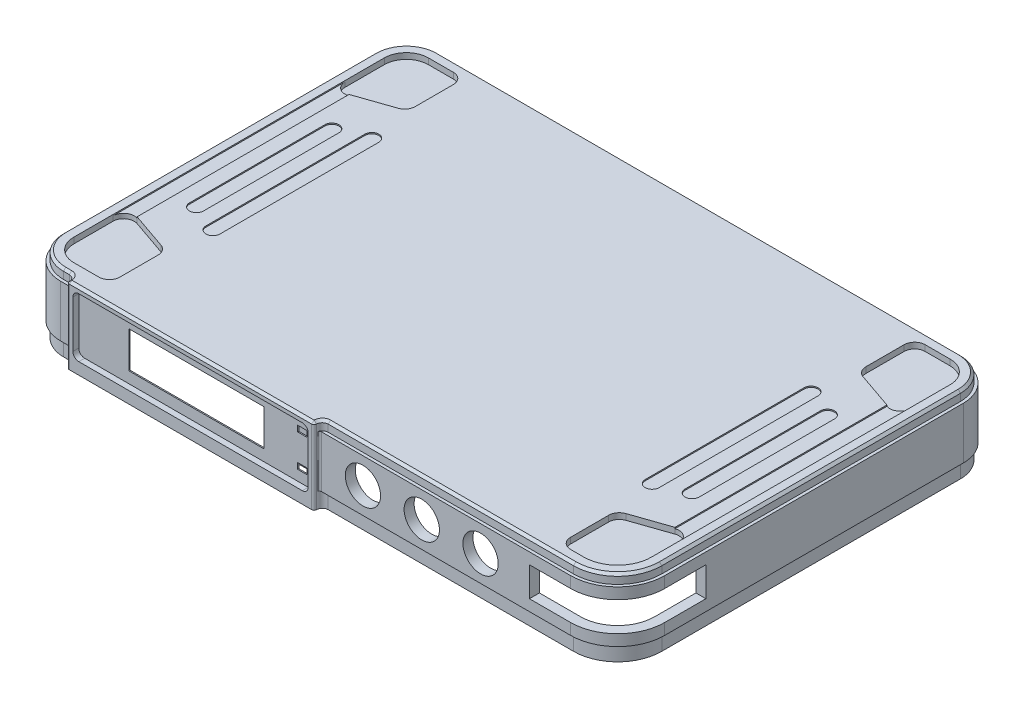
SolidWorks part; units mm, degrees
ref_plane "Front Plane" through (0, 0, 0) normal (0, 0, 1) x (1, 0, 0)
ref_plane "Top Plane" through (0, 0, 0) normal (0, 1, 0) x (1, 0, 0)
ref_plane "Right Plane" through (0, 0, 0) normal (1, 0, 0) x (0, 0, -1)
sketch "Sketch1" plane through (0, 0, 0) normal (0, 1, 0) x (1, 0, 0)
  line L0 (-50.35, 0) -> (50.35, 0) construction
  line L1 (0, 32.39) -> (0, -32.39) construction
  line L8 (44.35, 32.39) -> (-44.35, 32.39)
  line L9 (-50.35, 26.39) -> (-50.35, -26.39)
  line L10 (-44.35, -32.39) -> (42.35, -32.39)
  line L11 (50.35, -24.39) -> (50.35, 26.39)
  arc A2 (42.35, -32.39) -> (50.35, -24.39) centre (42.35, -24.39) ccw
  arc A8 (50.35, 26.39) -> (44.35, 32.39) centre (44.35, 26.39) ccw
  arc A9 (-44.35, 32.39) -> (-50.35, 26.39) centre (-44.35, 26.39) ccw
  arc A10 (-50.35, -26.39) -> (-44.35, -32.39) centre (-44.35, -26.39) ccw
  dimension "D2" = 64.78
  dimension "D3" = 6
  dimension "D1" = 100.7
  dimension "D4" = 0
  dimension "D5" = 8
extrude "Boss-Extrude1" add sketch "Sketch1" along normal blind 13
sketch "Sketch3" plane through (0, 13, 0) normal (0, 1, 0) x (1, 0, 0)
  line L0 (-50.35, 0) -> (50.35, 0) construction
  line L1 (-50.35, 26.39) -> (-50.35, -26.39) construction
  line L2 (42.35, -30.1389) -> (40.0989, -30.1389)
  line L3 (0, -32.39) -> (0, 32.39) construction
  line L4 (-44.35, -32.39) -> (42.35, -32.39) construction
  line L5 (50.35, -24.39) -> (50.35, 26.39) construction
  line L6 (-45.9859, -18.557) -> (-39.9859, -20.6263) construction
  line L8 (-48.0989, -19.7157) -> (-48.0989, -26.39)
  line L9 (-39.5121, -20.1524) -> (-45.7121, -18.014)
  line L10 (-38.2989, -28.3389) -> (-38.2989, -21.854)
  line L11 (-44.35, -30.1389) -> (-40.0989, -30.1389)
  line L13 (44.35, 32.39) -> (-44.35, 32.39) construction
  line L14 (-44.35, 30.1389) -> (-40.0989, 30.1389)
  line L15 (-38.2989, 28.3389) -> (-38.2989, 21.854)
  line L16 (-39.5121, 20.1524) -> (-45.7121, 18.014)
  line L17 (-48.0989, 19.7157) -> (-48.0989, 26.39)
  line L18 (48.0989, 19.7157) -> (48.0989, 26.39)
  line L19 (39.5121, 20.1524) -> (45.7121, 18.014)
  line L20 (38.2989, 28.3389) -> (38.2989, 21.854)
  line L21 (44.35, 30.1389) -> (40.0989, 30.1389)
  line L23 (38.2989, -28.3389) -> (38.2989, -21.854)
  line L24 (39.5121, -20.1524) -> (45.7121, -18.014)
  line L25 (48.0989, -19.7157) -> (48.0989, -24.39)
  arc A0 (-40.0989, 30.1389) -> (-38.2989, 28.3389) centre (-40.0989, 28.3389) cw
  arc A1 (-38.2989, 21.854) -> (-39.5121, 20.1524) centre (-40.0989, 21.854) cw
  arc A2 (-45.7121, 18.014) -> (-48.0989, 19.7157) centre (-46.2989, 19.7157) cw
  arc A3 (-48.0989, 26.39) -> (-44.35, 30.1389) centre (-44.35, 26.39) cw
  arc A4 (-50.35, -26.39) -> (-44.35, -32.39) centre (-44.35, -26.39) ccw construction
  arc A5 (42.35, -32.39) -> (50.35, -24.39) centre (42.35, -24.39) ccw construction
  arc A6 (38.2989, -28.3389) -> (40.0989, -30.1389) centre (40.0989, -28.3389) ccw
  arc A8 (-48.0989, -26.39) -> (-44.35, -30.1389) centre (-44.35, -26.39) ccw
  arc A9 (-45.7121, -18.014) -> (-48.0989, -19.7157) centre (-46.2989, -19.7157) ccw
  arc A10 (-38.2989, -21.854) -> (-39.5121, -20.1524) centre (-40.0989, -21.854) ccw
  arc A11 (-40.0989, -30.1389) -> (-38.2989, -28.3389) centre (-40.0989, -28.3389) ccw
  arc A13 (38.2989, -21.854) -> (39.5121, -20.1524) centre (40.0989, -21.854) cw
  arc A14 (45.7121, -18.014) -> (48.0989, -19.7157) centre (46.2989, -19.7157) cw
  arc A15 (48.0989, -24.39) -> (42.35, -30.1389) centre (42.35, -24.39) cw
  arc A16 (48.0989, 26.39) -> (44.35, 30.1389) centre (44.35, 26.39) ccw
  arc A17 (45.7121, 18.014) -> (48.0989, 19.7157) centre (46.2989, 19.7157) ccw
  arc A18 (38.2989, 21.854) -> (39.5121, 20.1524) centre (40.0989, 21.854) ccw
  arc A19 (40.0989, 30.1389) -> (38.2989, 28.3389) centre (40.0989, 28.3389) ccw
  point P64 (-38.8262, -29.6117)
  point P65 (-47.3438, -18.25)
  point P66 (-38.6333, -20.8091)
  point P67 (-47.0009, -29.0409)
  point P68 (-38.6333, 20.8091)
  point P75 (-47.3438, 18.25)
  dimension "D3" = 36.5
  dimension "D1" = 1.8
  dimension "D6" = 0
  dimension "D7" = 0
  dimension "D2" = 9.8
  dimension "D5" = 14.2
  dimension "D9" = 4.2511
extrude "Cut-Extrude1" cut sketch "Sketch3" against normal blind 1 contours L11 A11 L10 A10 L9 A9 L8 A8 | A15 L25 A14 L24 A13 L23 A6 L2 | L21 A19 L20 A18 L19 A17 L18 A16 | A3 L17 A2 L16 A1 L15 A0 L14 region at (43.195, 13, 24.2277) region at (-43.3228, 13, 24.3948) region at (-43.3228, 13, -24.3948) region at (43.3228, 13, -24.3948)
sketch "Sketch4" plane through (0, 13, 0) normal (0, 1, 0) x (1, 0, 0)
  line L0 (-48.0989, 19.7157) -> (-48.0989, -19.7157)
  line L1 (-45.7121, 0) -> (-48.0989, 0) construction
  line L2 (-40.9252, 0) -> (-43.3121, 0) construction
  line L3 (-42.1186, 11.5066) -> (-42.1186, -11.5066) construction
  line L4 (-40.9252, 11.5066) -> (-40.9252, -11.5066)
  line L5 (-45.7121, 18.014) -> (-45.7121, -18.014)
  line L6 (-43.3121, 11.5066) -> (-43.3121, -11.5066)
  line L7 (-37.3317, 13.5066) -> (-37.3317, -13.5066) construction
  line L8 (-36.1383, 13.5066) -> (-36.1383, -13.5066)
  line L9 (-38.5252, 13.5066) -> (-38.5252, -13.5066)
  line L10 (-36.1383, 0) -> (-38.5252, 0) construction
  line L11 (-45.7121, 0) -> (-43.3121, 0) construction
  line L12 (-40.9252, 0) -> (-38.5252, 0) construction
  line L13 (0, 32.39) -> (0, -32.39) construction
  line L14 (44.35, 32.39) -> (-44.35, 32.39) construction
  line L16 (42.1186, 11.5066) -> (42.1186, -11.5066) construction
  line L17 (40.9252, 11.5066) -> (40.9252, -11.5066)
  line L18 (43.3121, 11.5066) -> (43.3121, -11.5066)
  line L19 (37.3317, 13.5066) -> (37.3317, -13.5066) construction
  line L20 (36.1383, 13.5066) -> (36.1383, -13.5066)
  line L21 (38.5252, 13.5066) -> (38.5252, -13.5066)
  line L22 (40.9252, 0) -> (38.5252, 0) construction
  line L23 (45.7121, 0) -> (43.3121, 0) construction
  line L24 (36.1383, 0) -> (38.5252, 0) construction
  line L25 (40.9252, 0) -> (43.3121, 0) construction
  line L26 (45.7121, 0) -> (48.0989, 0) construction
  line L27 (45.7121, 18.014) -> (45.7121, -18.014)
  line L28 (48.0989, 19.7157) -> (48.0989, -19.7157)
  arc A0 (-48.0989, 19.7157) -> (-45.7121, 18.014) centre (-46.2989, 19.7157) ccw construction
  arc A1 (-45.7121, -18.014) -> (-48.0989, -19.7157) centre (-46.2989, -19.7157) ccw construction
  arc A2 (-48.0989, 19.7157) -> (-45.7121, 18.014) centre (-46.2989, 19.7157) ccw
  arc A3 (-45.7121, -18.014) -> (-48.0989, -19.7157) centre (-46.2989, -19.7157) ccw
  arc A4 (-40.9252, 11.5066) -> (-43.3121, 11.5066) centre (-42.1186, 11.5066) ccw
  arc A5 (-43.3121, -11.5066) -> (-40.9252, -11.5066) centre (-42.1186, -11.5066) ccw
  arc A6 (-36.1383, 13.5066) -> (-38.5252, 13.5066) centre (-37.3317, 13.5066) ccw
  arc A7 (-38.5252, -13.5066) -> (-36.1383, -13.5066) centre (-37.3317, -13.5066) ccw
  arc A8 (40.9252, 11.5066) -> (43.3121, 11.5066) centre (42.1186, 11.5066) cw
  arc A9 (43.3121, -11.5066) -> (40.9252, -11.5066) centre (42.1186, -11.5066) cw
  arc A10 (36.1383, 13.5066) -> (38.5252, 13.5066) centre (37.3317, 13.5066) cw
  arc A11 (38.5252, -13.5066) -> (36.1383, -13.5066) centre (37.3317, -13.5066) cw
  arc A12 (45.7121, -18.014) -> (48.0989, -19.7157) centre (46.2989, -19.7157) cw
  arc A13 (48.0989, 19.7157) -> (45.7121, 18.014) centre (46.2989, 19.7157) cw
  point P4 (-42.1186, 0)
  point P10 (-42.1186, 12.7)
  point P11 (-42.1186, -12.7)
  point P17 (-37.3317, 0)
  point P28 (-37.3317, -14.7)
  point P29 (-37.3317, 14.7)
  point P38 (42.1186, 0)
  point P45 (37.3317, 0)
  point P62 (37.3317, 14.7)
  point P63 (37.3317, -14.7)
  point P64 (42.1186, -12.7)
  point P65 (42.1186, 12.7)
  dimension "D1" = 8.0188
  dimension "D2" = 2.4
  dimension "D3" = 25.4
  dimension "D4" = 29.4
extrude "Cut-Extrude2" cut sketch "Sketch4" against normal blind 0.2
sketch "Sketch5" plane through (0, 13, 0) normal (0, 1, 0) x (1, 0, 0)
  line L0 (44.35, 31.89) -> (-44.35, 31.89)
  line L1 (-49.85, 26.39) -> (-49.85, -26.39)
  line L2 (-44.35, -31.89) -> (42.35, -31.89)
  line L3 (49.85, -24.39) -> (49.85, 26.39)
  line L4 (44.35, 32.39) -> (-44.35, 32.39)
  line L5 (-50.35, 26.39) -> (-50.35, -26.39)
  line L6 (-44.35, -32.39) -> (42.35, -32.39)
  line L7 (50.35, -24.39) -> (50.35, 26.39)
  line L8 (44.35, 32.39) -> (-44.35, 32.39)
  line L9 (-50.35, 26.39) -> (-50.35, -26.39)
  line L10 (-44.35, -32.39) -> (42.35, -32.39)
  line L11 (50.35, -24.39) -> (50.35, 26.39)
  arc A0 (-44.35, 31.89) -> (-49.85, 26.39) centre (-44.35, 26.39) ccw
  arc A1 (-49.85, -26.39) -> (-44.35, -31.89) centre (-44.35, -26.39) ccw
  arc A2 (42.35, -31.89) -> (49.85, -24.39) centre (42.35, -24.39) ccw
  arc A3 (49.85, 26.39) -> (44.35, 31.89) centre (44.35, 26.39) ccw
  arc A4 (50.35, 26.39) -> (44.35, 32.39) centre (44.35, 26.39) ccw
  arc A5 (-44.35, 32.39) -> (-50.35, 26.39) centre (-44.35, 26.39) ccw
  arc A6 (-50.35, -26.39) -> (-44.35, -32.39) centre (-44.35, -26.39) ccw
  arc A7 (42.35, -32.39) -> (50.35, -24.39) centre (42.35, -24.39) ccw
  arc A8 (50.35, 26.39) -> (44.35, 32.39) centre (44.35, 26.39) ccw
  arc A9 (-44.35, 32.39) -> (-50.35, 26.39) centre (-44.35, 26.39) ccw
  arc A10 (-50.35, -26.39) -> (-44.35, -32.39) centre (-44.35, -26.39) ccw
  arc A11 (42.35, -32.39) -> (50.35, -24.39) centre (42.35, -24.39) ccw
  dimension "D2" = 0.5
  dimension "D1" = 0
extrude "Cut-Extrude3" cut sketch "Sketch5" against normal blind 1.6
sketch "Sketch6" plane through (0, 0, 0) normal (0, -1, 0) x (1, 0, 0)
  line L4 (-44.35, -32.39) -> (44.35, -32.39)
  line L5 (-50.35, 26.39) -> (-50.35, -26.39)
  line L6 (42.35, 32.39) -> (-44.35, 32.39)
  line L7 (50.35, -26.39) -> (50.35, 24.39)
  line L8 (-44.35, -32.39) -> (44.35, -32.39)
  line L9 (-50.35, 26.39) -> (-50.35, -26.39)
  line L10 (42.35, 32.39) -> (-44.35, 32.39)
  line L11 (50.35, -26.39) -> (50.35, 24.39)
  line L12 (49.85, -26.39) -> (49.85, 24.39)
  line L13 (-44.35, -31.89) -> (44.35, -31.89)
  line L14 (-49.85, 26.39) -> (-49.85, -26.39)
  line L15 (42.35, 31.89) -> (-44.35, 31.89)
  line L16 (49.85, -26.39) -> (49.85, 24.39)
  line L17 (-44.35, -31.89) -> (44.35, -31.89)
  line L18 (-49.85, 26.39) -> (-49.85, -26.39)
  line L19 (42.35, 31.89) -> (-44.35, 31.89)
  arc A4 (44.35, -32.39) -> (50.35, -26.39) centre (44.35, -26.39) ccw
  arc A5 (-50.35, -26.39) -> (-44.35, -32.39) centre (-44.35, -26.39) ccw
  arc A6 (-44.35, 32.39) -> (-50.35, 26.39) centre (-44.35, 26.39) ccw
  arc A7 (50.35, 24.39) -> (42.35, 32.39) centre (42.35, 24.39) ccw
  arc A8 (44.35, -32.39) -> (50.35, -26.39) centre (44.35, -26.39) ccw
  arc A9 (-50.35, -26.39) -> (-44.35, -32.39) centre (-44.35, -26.39) ccw
  arc A10 (-44.35, 32.39) -> (-50.35, 26.39) centre (-44.35, 26.39) ccw
  arc A11 (50.35, 24.39) -> (42.35, 32.39) centre (42.35, 24.39) ccw
  arc A12 (44.35, -31.89) -> (49.85, -26.39) centre (44.35, -26.39) ccw
  arc A13 (-49.85, -26.39) -> (-44.35, -31.89) centre (-44.35, -26.39) ccw
  arc A14 (-44.35, 31.89) -> (-49.85, 26.39) centre (-44.35, 26.39) ccw
  arc A15 (49.85, 24.39) -> (42.35, 31.89) centre (42.35, 24.39) ccw
  arc A16 (44.35, -31.89) -> (49.85, -26.39) centre (44.35, -26.39) ccw
  arc A17 (-49.85, -26.39) -> (-44.35, -31.89) centre (-44.35, -26.39) ccw
  arc A18 (-44.35, 31.89) -> (-49.85, 26.39) centre (-44.35, 26.39) ccw
  arc A19 (49.85, 24.39) -> (42.35, 31.89) centre (42.35, 24.39) ccw
  dimension "D1" = 0
  dimension "D2" = 0
extrude "Cut-Extrude4" cut sketch "Sketch6" against normal blind 2.6
sketch "Sketch7" plane through (0, 0, 31.89) normal (0, 0, 1) x (1, 0, 0)
  line L0 (-44.35, 13) -> (42.35, 13) construction
  line L1 (-42.35, 13) -> (-0.35, 13)
  line L2 (-42.35, 13) -> (-42.35, 0)
  line L3 (-42.35, 0) -> (-0.35, 0)
  line L4 (-0.35, 13) -> (-0.35, 0)
  line L5 (-42.35, 13) -> (-0.35, 0) construction
  line L6 (-42.35, 0) -> (-0.35, 13) construction
  line L7 (42.35, 0) -> (-44.35, 0) construction
  line L8 (-50.35, 11.4) -> (-50.35, 2.6) construction
  point P0 (-21.35, 6.5)
  dimension "D1" = 42
  dimension "D2" = 8
extrude "Boss-Extrude2" add sketch "Sketch7" along normal blind 1.4
sketch "Sketch8" plane through (-49.85, 0, 0) normal (-1, 0, 0) x (0, 0, 1)
  line L0 (0, 0) -> (0, 13) construction
  line L1 (26.39, 0) -> (-26.39, 0) construction
  line L2 (-26.39, 13) -> (26.39, 13) construction
  line L4 (-18, 11.4) -> (-18, 2.6) construction
  line L5 (-26.39, 11.4) -> (26.39, 11.4) construction
  line L6 (26.39, 2.6) -> (-26.39, 2.6) construction
  circle A0 centre (-18, 7) radius 6
  circle A1 centre (18, 7) radius 6
  circle A2 centre (0, 7) radius 6
  point P8 (-24, 7)
  point P13 (-7.39, 6.5)
  point P16 (7.39, 6.5)
  point P17 (24, 7)
  line M5 (-26.39, 11.4) -> (26.39, 11.4)
  dimension "D1" = 12
  dimension "D2" = 18
extrude "Cut-Extrude6" cut sketch "Sketch8" along normal up to surface (0.5 mm away) contours A0 M5 | A1 M5 | A2 M5 region at (-49.85, 6.5654, -18) region at (-49.85, 6.5654, 18) region at (-49.85, 6.5654, 0) up to face at (-50.35, 7, 0)
sketch "Sketch9" plane through (0, 0, 33.29) normal (0, 0, 1) x (1, 0, 0)
  line L0 (-42.35, 0) -> (-0.35, 0) construction
  line L1 (-40.35, 12) -> (-2.35, 12)
  line L2 (-41.35, 11) -> (-41.35, 3)
  line L3 (-40.35, 2) -> (-2.35, 2)
  line L4 (-1.35, 11) -> (-1.35, 3)
  line L5 (-41.35, 12) -> (-1.35, 2) construction
  line L6 (-41.35, 2) -> (-1.35, 12) construction
  line L7 (-42.35, 7) -> (-0.35, 7) construction
  line L8 (-42.35, 11.4) -> (-42.35, 2.6) construction
  line L9 (-0.35, 2.6) -> (-0.35, 11.4) construction
  line L10 (-21.35, 13) -> (-21.35, 0) construction
  line L11 (-0.35, 13) -> (-42.35, 13) construction
  arc A0 (-40.35, 12) -> (-41.35, 11) centre (-40.35, 11) ccw
  arc A1 (-41.35, 3) -> (-40.35, 2) centre (-40.35, 3) ccw
  arc A2 (-1.35, 3) -> (-2.35, 2) centre (-2.35, 3) cw
  arc A3 (-2.35, 12) -> (-1.35, 11) centre (-2.35, 11) cw
  point P0 (-21.35, 7)
  dimension "D4" = 1
  dimension "D1" = 2
  dimension "D2" = 10
  dimension "D3" = 40
extrude "Cut-Extrude7" cut sketch "Sketch9" against normal blind 1
sketch "Sketch10" plane through (0, 0, -31.89) normal (0, 0, -1) x (-1, 0, 0)
  line L0 (-23.85, 6.5) -> (-34.85, 6.5) construction
  line L1 (-23.85, 0) -> (-34.85, 0)
  line L2 (-23.85, 13) -> (-34.85, 13)
  line L3 (-29.35, 11.4) -> (-29.35, 2.6) construction
  line L4 (-44.35, 11.4) -> (44.35, 11.4) construction
  line L5 (-50.35, 11.4) -> (-50.35, 2.6) construction
  line L6 (44.35, 2.6) -> (-44.35, 2.6) construction
  line L7 (44.35, 0) -> (-44.35, 0) construction
  line L9 (50.35, 11.4) -> (50.35, 2.6) construction
  line L10 (-44.35, 13) -> (44.35, 13) construction
  arc A0 (-23.85, 0) -> (-23.85, 13) centre (-23.85, 6.5) ccw
  arc A1 (-34.85, 13) -> (-34.85, 0) centre (-34.85, 6.5) ccw
  circle A2 centre (33.85, 6.5) radius 6.5
  circle A3 centre (-34.85, 6.5) radius 5 construction
  point P2 (-29.35, 6.5)
  point P7 (-17.35, 6.5)
  point P14 (-41.35, 6.5)
  point P23 (-34.85, 11.5)
  point P24 (40.35, 6.5)
  dimension "D2" = 24
  dimension "D3" = 11
  dimension "D5" = 1.5
  dimension "D6" = 10
  dimension "D1" = 9
  dimension "D4" = 10
extrude "Cut-Extrude8" cut sketch "Sketch10" along normal up to surface (0.5 mm away) up to face at (0, 7, -32.39)
fillet "Fillet1" radius 0.4 4 edges at (-42.35, 7, 32.39) (-42.35, 6.5, 33.29) (-0.35, 7, 32.39) (-0.35, 6.5, 33.29)
fillet "Fillet2" radius 1 2 edges at (-0.35, 12.2, 31.89) (-42.35, 12.2, 31.89)
chamfer "Chamfer1" distance 0.4 angle 45 14 edges at (0, 13, -31.89) (48.2391, 13, -30.2791) (-48.2391, 13, -30.2791) (49.85, 13, -1) (-49.85, 13, 0) (47.6533, 13, 29.6933) (-48.2391, 13, 30.2791) (21.5, 13, 31.89) (-43.85, 13, 31.89) (-0.0571, 13, 32.1829) (-42.6429, 13, 32.1829) (-0.4672, 13, 33.1728) (-42.2328, 13, 33.1728) (-21.35, 13, 33.29)
sketch "Sketch11" plane through (0, 0, 0) normal (0, -1, 0) x (1, 0, 0)
  line L6 (-0.75, 33.29) -> (-41.95, 33.29)
  line L7 (-0.75, 33.29) -> (-41.95, 33.29)
  line L8 (-43.35, 31.89) -> (-44.35, 31.89)
  line L9 (-43.35, 31.89) -> (-44.35, 31.89)
  line L10 (-49.85, 26.39) -> (-49.85, -26.39)
  line L11 (-49.85, 26.39) -> (-49.85, -26.39)
  line L18 (-1.3994, 32.09) -> (-41.3006, 32.09)
  line L19 (-43.35, 30.69) -> (-44.35, 30.69)
  line L20 (-48.65, 26.39) -> (-48.65, -26.39)
  line L21 (-44.35, -30.69) -> (44.35, -30.69)
  line L22 (48.65, -26.39) -> (48.65, 24.39)
  line L23 (42.35, 30.69) -> (0.65, 30.69)
  line L24 (-44.35, -31.89) -> (44.35, -31.89)
  line L25 (-44.35, -31.89) -> (44.35, -31.89)
  line L26 (49.85, -26.39) -> (49.85, 24.39)
  line L27 (49.85, -26.39) -> (49.85, 24.39)
  line L28 (42.35, 31.89) -> (0.65, 31.89)
  line L29 (42.35, 31.89) -> (0.65, 31.89)
  arc A6 (-41.95, 33.29) -> (-42.35, 32.89) centre (-41.95, 32.89) ccw
  arc A7 (-41.95, 33.29) -> (-42.35, 32.89) centre (-41.95, 32.89) ccw
  arc A8 (-43.35, 31.89) -> (-42.35, 32.89) centre (-43.35, 32.89) ccw
  arc A9 (-43.35, 31.89) -> (-42.35, 32.89) centre (-43.35, 32.89) ccw
  arc A10 (-44.35, 31.89) -> (-49.85, 26.39) centre (-44.35, 26.39) ccw
  arc A11 (-44.35, 31.89) -> (-49.85, 26.39) centre (-44.35, 26.39) ccw
  arc A18 (-41.3006, 32.09) -> (-41.3006, 32.09) centre (-41.3006, 32.09) ccw
  arc A19 (-43.35, 30.69) -> (-41.3006, 32.09) centre (-43.35, 32.89) ccw
  arc A20 (-44.35, 30.69) -> (-48.65, 26.39) centre (-44.35, 26.39) ccw
  arc A21 (-48.65, -26.39) -> (-44.35, -30.69) centre (-44.35, -26.39) ccw
  arc A22 (44.35, -30.69) -> (48.65, -26.39) centre (44.35, -26.39) ccw
  arc A23 (48.65, 24.39) -> (42.35, 30.69) centre (42.35, 24.39) ccw
  arc A24 (-1.3994, 32.09) -> (0.65, 30.69) centre (0.65, 32.89) ccw
  arc A25 (-1.3994, 32.09) -> (-1.3994, 32.09) centre (-1.3994, 32.09) ccw
  arc A26 (-49.85, -26.39) -> (-44.35, -31.89) centre (-44.35, -26.39) ccw
  arc A27 (-49.85, -26.39) -> (-44.35, -31.89) centre (-44.35, -26.39) ccw
  arc A28 (44.35, -31.89) -> (49.85, -26.39) centre (44.35, -26.39) ccw
  arc A29 (44.35, -31.89) -> (49.85, -26.39) centre (44.35, -26.39) ccw
  arc A30 (49.85, 24.39) -> (42.35, 31.89) centre (42.35, 24.39) ccw
  arc A31 (49.85, 24.39) -> (42.35, 31.89) centre (42.35, 24.39) ccw
  arc A32 (-0.35, 32.89) -> (0.65, 31.89) centre (0.65, 32.89) ccw
  arc A33 (-0.35, 32.89) -> (0.65, 31.89) centre (0.65, 32.89) ccw
  arc A34 (-0.35, 32.89) -> (-0.75, 33.29) centre (-0.75, 32.89) ccw
  arc A35 (-0.35, 32.89) -> (-0.75, 33.29) centre (-0.75, 32.89) ccw
  point P10 (0, 0)
  point P11 (0, 0)
  dimension "D2" = 1.2
  dimension "D1" = 0
extrude "Cut-Extrude9" cut sketch "Sketch11" against normal blind 11.5 contours L18 A22 L23 A24 region at (-0.2395, 0, 0.2781)
sketch "Sketch12" plane through (0, 0, 32.29) normal (0, 0, 1) x (1, 0, 0)
  line L0 (-41.35, 7) -> (-1.35, 7) construction
  line L1 (-32.85, 10.1) -> (-9.85, 10.1)
  line L2 (-32.85, 10.1) -> (-32.85, 3.9)
  line L3 (-32.85, 3.9) -> (-9.85, 3.9)
  line L4 (-9.85, 10.1) -> (-9.85, 3.9)
  line L5 (-32.85, 10.1) -> (-9.85, 3.9) construction
  line L6 (-32.85, 3.9) -> (-9.85, 10.1) construction
  line L7 (-41.35, 11) -> (-41.35, 3) construction
  line L8 (-1.35, 3) -> (-1.35, 11) construction
  line L9 (-21.35, 12) -> (-21.35, 2) construction
  line L10 (-2.35, 12) -> (-40.35, 12) construction
  line L11 (-40.35, 2) -> (-2.35, 2) construction
  line L13 (-4.15, 10.25) -> (-2.55, 10.25)
  line L14 (-4.15, 10.25) -> (-4.15, 9.25)
  line L15 (-4.15, 9.25) -> (-2.55, 9.25)
  line L16 (-2.55, 10.25) -> (-2.55, 9.25)
  line L17 (-4.15, 10.25) -> (-2.55, 9.25) construction
  line L18 (-4.15, 9.25) -> (-2.55, 10.25) construction
  line L19 (-4.15, 4.75) -> (-2.55, 4.75)
  line L20 (-4.15, 4.75) -> (-4.15, 3.75)
  line L21 (-4.15, 3.75) -> (-2.55, 3.75)
  line L22 (-2.55, 4.75) -> (-2.55, 3.75)
  line L23 (-4.15, 4.75) -> (-2.55, 3.75) construction
  line L24 (-4.15, 3.75) -> (-2.55, 4.75) construction
  line L25 (-2.55, 10.25) -> (-2.55, 12) construction
  line L26 (-2.35, 12) -> (-40.35, 12) construction
  line L27 (-2.55, 3.75) -> (-2.55, 2) construction
  line L28 (-40.35, 2) -> (-2.35, 2) construction
  line L29 (-1.35, 3) -> (-1.35, 11) construction
  point P0 (-21.35, 7)
  point P17 (-3.35, 9.75)
  point P22 (-3.35, 4.25)
  dimension "D1" = 6.2
  dimension "D2" = 23
  dimension "D3" = 1
  dimension "D4" = 1.6
  dimension "D5" = 1.2
  dimension "D6" = 4.5
  dimension "D7" = 1.75
extrude "Cut-Extrude10" cut sketch "Sketch12" against normal blind 12
sketch "Sketch13" plane through (-49.85, 0, 0) normal (-1, 0, 0) x (0, 0, 1)
  circle A0 centre (-18, 7) radius 4
  circle A1 centre (18, 7) radius 4
  circle A2 centre (0, 7) radius 4
  dimension "D1" = 8
extrude "Cut-Extrude11" cut sketch "Sketch13" against normal blind 12
sketch "Sketch14" plane through (0, 0, -31.89) normal (0, 0, -1) x (-1, 0, 0)
  line L0 (-34.85, 6.5) -> (-21.7583, 6.5) construction
  line L1 (-30.967, 9.65) -> (-21.7583, 9.65)
  line L2 (-30.967, 3.35) -> (-21.7583, 3.35)
  circle A0 centre (33.85, 6.5) radius 2.25
  arc A2 (-21.7583, 3.35) -> (-21.7583, 9.65) centre (-21.7583, 6.5) ccw
  arc A3 (-30.967, 9.65) -> (-30.967, 3.35) centre (-34.85, 6.5) ccw
  arc A4 (-39.1208, 11.4) -> (-40.05, 2.6) centre (-34.85, 6.5) ccw construction
  arc A5 (-18.65, 2.6) -> (-19.5792, 11.4) centre (-23.85, 6.5) ccw construction
  point P13 (-17.3859, 7.1825)
  point P24 (-18.6083, 6.5)
  dimension "D1" = 4.4083
  dimension "D3" = 10
  dimension "D5" = 4.5
  dimension "D2" = 6.3
  dimension "D4" = 1.4
extrude "Cut-Extrude12" cut sketch "Sketch14" against normal blind 12
sketch "Sketch15" plane through (0, 0, 32.39) normal (0, 0, 1) x (1, 0, 0)
  line L0 (27.05, 7) -> (17.05, 7) construction
  line L1 (7.05, 7) -> (17.05, 7) construction
  line L2 (12.05, 11.4) -> (12.05, 2.6) construction
  line L3 (0.05, 11.4) -> (0.05, 2.6) construction
  line L4 (50.35, 11.4) -> (50.35, 2.6) construction
  line L5 (0.05, 11.4) -> (42.35, 11.4) construction
  line L6 (42.35, 2.6) -> (0.65, 2.6) construction
  line L7 (35.35, 9.5) -> (50.35, 9.5)
  line L8 (35.35, 9.5) -> (35.35, 4.5)
  line L9 (35.35, 4.5) -> (50.35, 4.5)
  line L10 (50.35, 9.5) -> (50.35, 4.5)
  line L11 (35.35, 9.5) -> (50.35, 4.5) construction
  line L12 (35.35, 4.5) -> (50.35, 9.5) construction
  circle A0 centre (7.05, 7) radius 3
  circle A1 centre (17.05, 7) radius 3
  circle A2 centre (27.05, 7) radius 3
  point P12 (20.05, 7)
  point P13 (12.05, 7)
  point P14 (4.05, 7)
  point P17 (42.85, 7)
  dimension "D1" = 6
  dimension "D2" = 16
  dimension "D3" = 10
  dimension "D4" = 4
  dimension "D5" = 15
  dimension "D6" = 5
extrude "Cut-Extrude13" cut sketch "Sketch15" against normal blind 15
sketch "Sketch18" plane through (0, 11.5, 0) normal (0, -1, 0) x (1, 0, 0)
  line L0 (-48.65, 26.39) -> (-48.65, 24.39) construction
  line L1 (-48.65, 26.39) -> (-48.65, -26.39) construction
  line L4 (-42.35, 30.69) -> (-44.35, 30.69) construction
  line L5 (0, 0) -> (0, 32.39) construction
  line L6 (0, 0) -> (-50.35, 0) construction
  line L7 (-41.85, 31.19) -> (-44.35, 31.19) construction
  line L8 (-49.15, 26.39) -> (-49.15, 23.89) construction
  line L9 (-45, 27.04) -> (-45.5657, 27.6057) construction
  line L10 (-42.35, 31.19) -> (-44.35, 31.19)
  line L11 (-49.15, 26.39) -> (-49.15, 24.39)
  line L14 (-49.15, 23.89) -> (-44.35, 23.89) construction
  line L15 (-41.85, 26.39) -> (-41.85, 31.19) construction
  line L16 (-48.65, 24.39) -> (-44.35, 24.39) construction
  line L17 (-42.35, 26.39) -> (-42.35, 30.69) construction
  line L18 (-42.35, 26.39) -> (-42.35, 31.19)
  line L19 (-44.35, 24.39) -> (-49.15, 24.39)
  line L20 (-6.35, 29.59) -> (-8.35, 29.59) construction
  line L22 (-45, -27.04) -> (-45.5657, -27.6057) construction
  line L23 (-42.35, -30.69) -> (-44.35, -30.69) construction
  line L24 (-48.65, -26.39) -> (-48.65, -24.39) construction
  line L25 (-44.35, -24.39) -> (-49.15, -24.39)
  line L26 (-42.35, -26.39) -> (-42.35, -31.19)
  line L27 (-49.15, -26.39) -> (-49.15, -24.39)
  line L28 (-42.35, -31.19) -> (-44.35, -31.19)
  line L29 (48.65, -26.39) -> (48.65, -24.39) construction
  line L30 (42.35, -30.69) -> (44.35, -30.69) construction
  line L31 (45, -27.04) -> (45.5657, -27.6057) construction
  line L32 (42.35, -31.19) -> (44.35, -31.19)
  line L33 (49.15, -26.39) -> (49.15, -24.39)
  line L34 (42.35, -26.39) -> (42.35, -31.19)
  line L35 (44.35, -24.39) -> (49.15, -24.39)
  line L36 (42.35, 30.69) -> (0.65, 30.69) construction
  line L38 (-8.35, 30.69) -> (-8.35, 28.49)
  line L39 (-8.35, 28.49) -> (-6.35, 28.49)
  line L40 (0.85, 30.69) -> (0.85, 28.49)
  line L41 (-50.35, 26.39) -> (-50.35, 22.0792) construction
  line L42 (-6.35, 28.49) -> (-6.35, 29.59)
  line L43 (-6.35, 29.59) -> (-1.15, 29.59)
  line L44 (-1.15, 28.49) -> (-1.15, 29.59)
  line L45 (-1.15, 29.59) -> (0.85, 29.59) construction
  line L46 (-3.75, 29.59) -> (-3.75, 30.69) construction
  line L47 (-1.15, 28.49) -> (0.85, 28.49)
  line L48 (42.35, 32.39) -> (0.05, 32.39) construction
  line L49 (0.85, 28.49) -> (0.85, 29.49) construction
  line L50 (-50.35, 13.9208) -> (-50.35, 4.0792) construction
  line L51 (33.35, 30.69) -> (33.35, 30.49)
  line L52 (-8.35, 30.69) -> (-1.15, 30.69)
  line L53 (30.05, 27.19) -> (28.35, 27.19)
  line L54 (28.35, 27.19) -> (28.35, 28.49)
  line L55 (28.35, 28.49) -> (30.05, 28.49)
  line L56 (32.05, 30.49) -> (32.05, 30.69)
  line L57 (32.05, 30.69) -> (33.35, 30.69)
  line L58 (42.35, 30.69) -> (0.65, 30.69) construction
  line L59 (48.65, 10.99) -> (43.05, 10.99)
  line L60 (48.65, 10.99) -> (48.65, 7.99)
  line L61 (48.65, 7.99) -> (43.05, 7.99)
  line L62 (43.05, 10.99) -> (43.05, 7.99)
  line L63 (50.35, -26.39) -> (50.35, 24.39) construction
  line L64 (48.65, -26.39) -> (48.65, 24.39) construction
  line L65 (-1.15, 30.69) -> (-1.15, 31.89)
  line L66 (-1.15, 31.89) -> (0.85, 31.89)
  line L67 (0.85, 30.69) -> (0.85, 31.89)
  line L68 (42.35, 31.89) -> (0.65, 31.89) construction
  arc A0 (-42.35, 26.39) -> (-44.35, 24.39) centre (-44.35, 26.39) cw
  arc A1 (-44.35, 31.19) -> (-49.15, 26.39) centre (-44.35, 26.39) ccw
  circle A3 centre (-45, 27.04) radius 0.8
  arc A4 (-44.35, 32.39) -> (-50.35, 26.39) centre (-44.35, 26.39) ccw construction
  arc A5 (-44.35, 30.69) -> (-48.65, 26.39) centre (-44.35, 26.39) ccw construction
  arc A7 (-41.85, 26.39) -> (-44.35, 23.89) centre (-44.35, 26.39) cw construction
  arc A8 (-44.35, -30.69) -> (-48.65, -26.39) centre (-44.35, -26.39) cw construction
  circle A9 centre (-45, -27.04) radius 0.8
  arc A10 (-44.35, -31.19) -> (-49.15, -26.39) centre (-44.35, -26.39) cw
  arc A11 (-42.35, -26.39) -> (-44.35, -24.39) centre (-44.35, -26.39) ccw
  arc A12 (44.35, -30.69) -> (48.65, -26.39) centre (44.35, -26.39) ccw construction
  arc A13 (42.35, -26.39) -> (44.35, -24.39) centre (44.35, -26.39) cw
  arc A14 (44.35, -31.19) -> (49.15, -26.39) centre (44.35, -26.39) ccw
  circle A15 centre (45, -27.04) radius 0.8
  arc A16 (33.35, 30.49) -> (30.05, 27.19) centre (30.05, 30.49) cw
  arc A17 (32.05, 30.49) -> (30.05, 28.49) centre (30.05, 30.49) cw
  arc A18 (-44.35, 30.69) -> (-48.65, 26.39) centre (-44.35, 26.39) ccw construction
  point P18 (-48.5926, 30.6326)
  point P20 (-45.5657, 27.6057)
  point P29 (-45, 27.04)
  point P39 (-8.35, 29.59)
  point P59 (-45, -27.04)
  point P60 (-45.5657, -27.6057)
  point P61 (-48.5926, -30.6326)
  point P76 (48.5926, -30.6326)
  point P77 (45.5657, -27.6057)
  point P78 (45, -27.04)
  point P100 (0, 0)
  point P101 (0, 0)
  point P105 (0, 0)
  point P108 (43.05, 9.49)
  point P112 (0, 0)
  point P113 (0, 0)
  arc M26 (44.35, -30.69) -> (48.65, -26.39) centre (44.35, -26.39) ccw
  line M28 (42.35, 30.69) -> (0.65, 30.69)
  line M95 (-44.35, -30.69) -> (34.85, -30.69)
  line M96 (34.85, -30.69) -> (44.35, -30.69)
  line M97 (48.65, -26.39) -> (48.65, 24.39)
  arc M99 (-44.35, 30.69) -> (-48.65, 26.39) centre (-44.35, 26.39) ccw
  line M100 (-48.65, 26.39) -> (-48.65, -26.39)
  arc M101 (-48.65, -26.39) -> (-44.35, -30.69) centre (-44.35, -26.39) ccw
  arc M102 (-41.3006, 32.09) -> (-43.35, 30.69) centre (-43.35, 32.89) cw
  line M103 (-43.35, 30.69) -> (-44.35, 30.69)
  dimension "D1" = 42
  dimension "D5" = 1.6
  dimension "D7" = 2
  dimension "D9" = 2.2
  dimension "D11" = 1
  dimension "D13" = 1.3
  dimension "D14" = 1.3
  dimension "D12" = 5
  dimension "D16" = 2
  dimension "D3" = 2.9192
  dimension "D22" = 0.2
  dimension "D2" = 9.2
  dimension "D4" = 90
  dimension "D6" = 0
  dimension "D8" = 0.5
  dimension "D10" = 2
  dimension "D15" = 31.2
  dimension "D17" = 3
  dimension "D18" = 7.3
  dimension "D19" = 24.4
  dimension "D20" = 54.08
  dimension "D21" = 2.65
  dimension "D23" = 1.7
  dimension "D24" = 1.2
extrude "Boss-Extrude6" add sketch "Sketch18" along normal blind 8.5 contours L59 L62 L61 M97 | L44 L47 L40 L38 L39 L42 L43 M28 | A0 L18 L19 A3 M102 M103 M99 M100 | A13 L34 L35 A15 M96 M26 M97 | L26 A11 L25 A9 M100 M101 M95 | L56 A17 L55 L54 L53 A16 L51 M28 region at (45.85, 11.5, 9.49) region at (42.4391, 11.5, -28.54) region at (-46.5, 11.5, -24.4791) region at (-42.4408, 11.5, 28.6602) region at (-3.2394, 11.5, 30.0171) region at (31.0806, 11.5, 28.5687)
fillet "Fillet6" radius 1 2 edges at (43.05, 7.25, 10.99) (43.05, 7.25, 7.99)
sketch "Sketch19" plane through (0, 3, 0) normal (0, -1, 0) x (1, 0, 0)
  line L0 (45.05, 9.49) -> (45.05, 7.9899) construction
  line L1 (43.05, 9.99) -> (43.05, 8.99) construction
  line L2 (48.65, 10.99) -> (44.05, 10.99) construction
  line L5 (45.05, 9.49) -> (45.05, 10.99) construction
  circle A0 centre (45.05, 9.49) radius 0.6
  point P3 (0, 0)
  point P4 (0, 0)
  point P5 (0, 0)
  point P6 (45, -27.04)
  point P8 (0, 0)
  point P12 (45.05, 9.49)
  point P16 (45.2695, -28.003)
  dimension "D1" = 1.2
  dimension "D2" = 36.53
  dimension "D3" = 2
extrude "Boss-Extrude7" add sketch "Sketch19" along normal blind 1.4
chamfer "Chamfer2" distance 0.4 angle 45 1 edges at (45.05, 1.6, 8.89)
sketch "Sketch20" plane through (0, 0, 29.59) normal (0, 0, -1) x (-1, 0, 0)
  line L0 (4.15, 4.75) -> (4.15, 3.75) construction
  line L1 (4.15, 3.75) -> (2.55, 3.75) construction
  line L2 (2.55, 3.75) -> (2.55, 4.75) construction
  line L3 (2.55, 4.75) -> (4.15, 4.75) construction
  line L4 (4.15, 10.25) -> (4.15, 9.25) construction
  line L5 (4.15, 9.25) -> (2.55, 9.25) construction
  line L6 (2.55, 9.25) -> (2.55, 10.25) construction
  line L7 (2.55, 10.25) -> (4.15, 10.25) construction
  line L8 (4.15, 4.75) -> (4.15, 3.75)
  line L9 (4.15, 3.75) -> (2.55, 3.75)
  line L10 (2.55, 3.75) -> (2.55, 4.75)
  line L11 (2.55, 4.75) -> (4.15, 4.75)
  line L12 (4.15, 10.25) -> (4.15, 9.25)
  line L13 (4.15, 9.25) -> (2.55, 9.25)
  line L14 (2.55, 9.25) -> (2.55, 10.25)
  line L15 (2.55, 10.25) -> (4.15, 10.25)
extrude "Cut-Extrude14" cut sketch "Sketch20" against normal up to surface (1.1 mm away) up to face at (-4.75, 7.25, 30.69)
sketch "Sketch22" plane through (0, 0, 0) normal (0, -1, 0) x (1, 0, 0)
  line L0 (0.65, 31.89) -> (0.65, 30.69)
  line L1 (-43.35, 31.89) -> (-43.35, 30.69)
  line L2 (-41.95, 33.29) -> (-0.75, 33.29) construction
  line L3 (-41.95, 33.29) -> (-0.75, 33.29)
  line L4 (-43.35, 30.69) -> (0.65, 30.69)
  arc A0 (-0.35, 32.89) -> (0.65, 31.89) centre (0.65, 32.89) ccw construction
  arc A1 (-41.95, 33.29) -> (-42.35, 32.89) centre (-41.95, 32.89) ccw construction
  arc A2 (-43.35, 31.89) -> (-42.35, 32.89) centre (-43.35, 32.89) ccw construction
  arc A3 (-0.35, 32.89) -> (-0.75, 33.29) centre (-0.75, 32.89) ccw construction
  arc A4 (-41.95, 33.29) -> (-42.35, 32.89) centre (-41.95, 32.89) ccw
  arc A5 (-43.35, 31.89) -> (-42.35, 32.89) centre (-43.35, 32.89) ccw
  arc A6 (-0.35, 32.89) -> (-0.75, 33.29) centre (-0.75, 32.89) ccw
  arc A7 (-0.35, 32.89) -> (0.65, 31.89) centre (0.65, 32.89) ccw
extrude "Boss-Extrude9" add sketch "Sketch22" against normal blind 1
